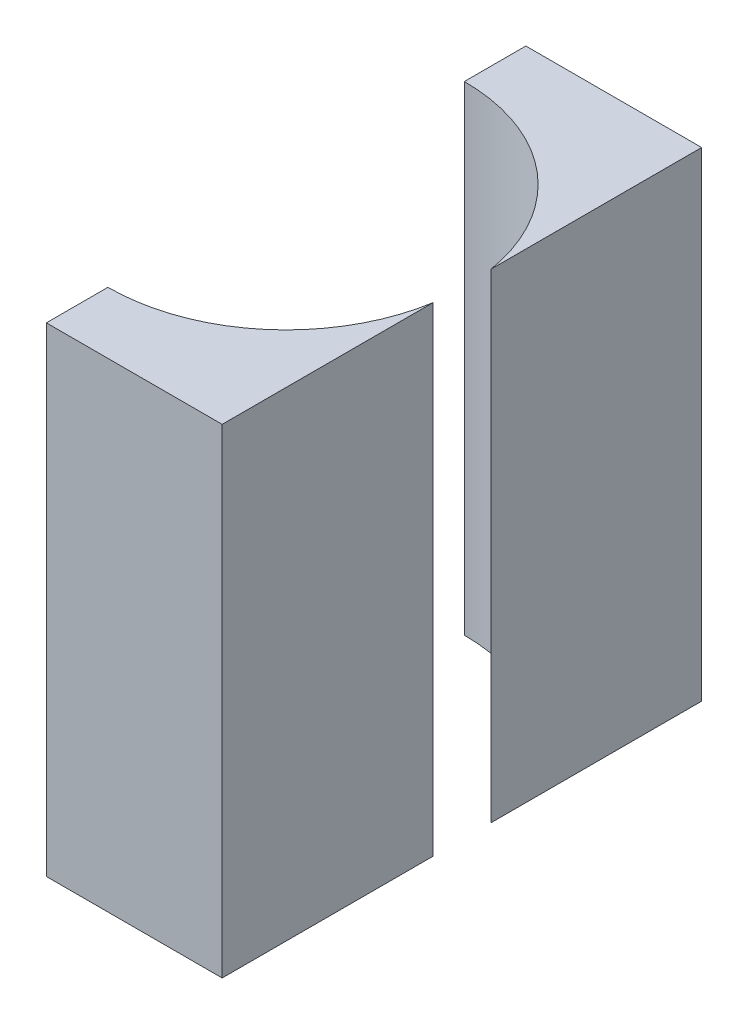
SolidWorks part; units mm, degrees
ref_plane "Front Plane" through (0, 0, 0) normal (0, 0, 1) x (1, 0, 0)
ref_plane "Top Plane" through (0, 0, 0) normal (0, 1, 0) x (1, 0, 0)
ref_plane "Right Plane" through (0, 0, 0) normal (1, 0, 0) x (0, 0, -1)
sketch "Sketch1" plane through (0, 86.6691, 0) normal (0, 1, 0) x (1, 0, 0)
  line L0 (245.7875, 7.2467) -> (234.7875, 7.2467)
  line L1 (234.7875, 7.2467) -> (234.7875, 11.0967)
  line L2 (234.8652, 22.2467) -> (-49765.1348, 22.2467) construction
  line L3 (245.7875, 37.2467) -> (234.7875, 37.2467)
  line L4 (234.7875, 37.2467) -> (234.7875, 33.3967)
  line L5 (245.7875, 7.2467) -> (245.7875, 37.2467)
  circle A0 centre (234.7875, 22.2467) radius 11 construction
  circle A1 centre (234.7875, 22.2467) radius 11
  circle A2 centre (234.7875, 22.2467) radius 11.15
  line M7 (245.7875, 33.2467) -> (245.7875, 11.2467)
  dimension "D1" = 0.15
extrude "Boss-Extrude1" add sketch "Sketch1" against normal up to surface (30 mm away) contours A2 L1 L0 L5 M7 | A2 L5 L3 L4 M7 region at (241.4126, 86.6691, -10.7637) region at (241.4126, 86.6691, -33.7297)
